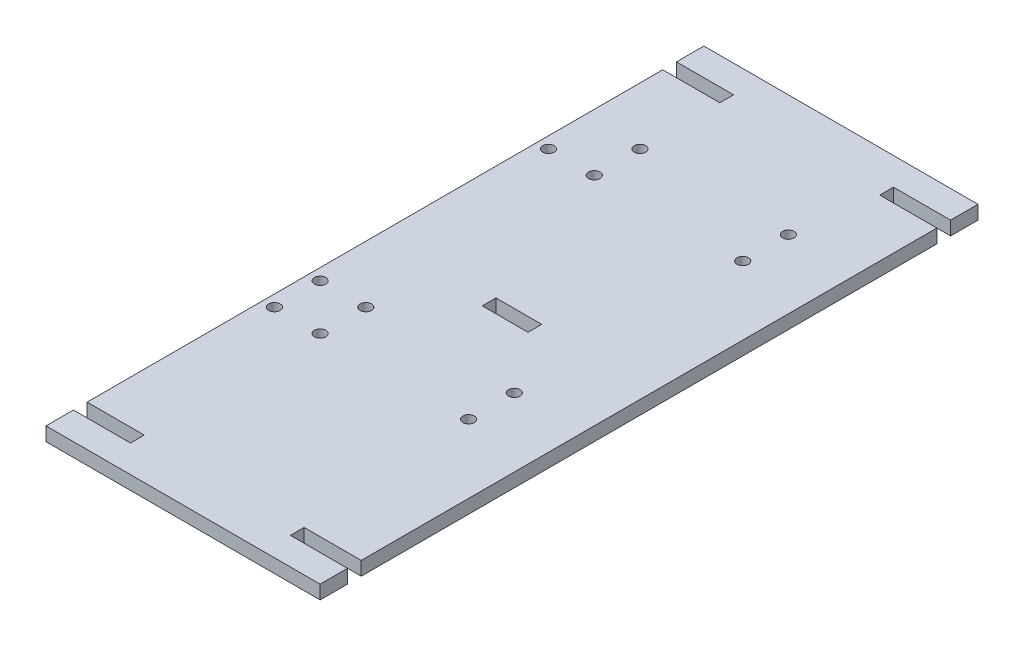
SolidWorks part; units mm, degrees
ref_plane "Front" through (0, 0, 0) normal (0, 0, 1) x (1, 0, 0)
ref_plane "Top" through (0, 0, 0) normal (0, 1, 0) x (1, 0, 0)
ref_plane "Right" through (0, 0, 0) normal (1, 0, 0) x (0, 0, -1)
sketch "Sketch1" plane through (0, 0, 0) normal (0, 1, 0) x (1, 0, 0)
  line L1 (0, 0) -> (-120, 0)
  line L2 (0, 0) -> (0, 288)
  line L3 (0, 288) -> (-120, 288)
  line L4 (-120, 0) -> (-120, 288)
  dimension "D1" = 288
  dimension "D2" = 120
extrude "Boss-Extrude1" add sketch "Sketch1" along normal blind 6
sketch "Sketch2" plane through (0, 6, 0) normal (0, 1, 0) x (1, 0, 0)
  line L0 (-120, 288) -> (-120, 0) construction
  line L1 (-120, 276) -> (-95, 276)
  line L2 (-120, 276) -> (-120, 270)
  line L3 (-120, 270) -> (-95, 270)
  line L4 (-95, 276) -> (-95, 270)
  line L5 (0, 288) -> (-120, 288) construction
  dimension "D1" = 6
  dimension "D2" = 25
  dimension "D3" = 12
extrude "Cut-Extrude1" cut sketch "Sketch2" against normal through all
pattern_linear "LPattern1" count 2 spacing 258 along (0, 0, 1) count 2 spacing 95 along (1, 0, 0) of "Cut-Extrude1"
sketch "Sketch3" plane through (0, 6, 0) normal (0, 1, 0) x (1, 0, 0)
  line L0 (-60, 288) -> (-60, 0) construction
  line L1 (0, 288) -> (-120, 288) construction
  line L2 (-120, 0) -> (0, 0) construction
  line L3 (-120, 144) -> (0, 144) construction
  line L4 (-120, 270) -> (-120, 18) construction
  line L5 (0, 18) -> (0, 270) construction
  line L7 (-70, 141) -> (-50, 141)
  line L8 (-70, 141) -> (-70, 147)
  line L9 (-70, 147) -> (-50, 147)
  line L10 (-50, 141) -> (-50, 147)
  line L11 (-70, 141) -> (-50, 147) construction
  line L12 (-70, 147) -> (-50, 141) construction
  point P12 (-60, 144)
  dimension "D1" = 6
  dimension "D2" = 20
extrude "Cut-Extrude2" cut sketch "Sketch3" against normal blind 10
sketch "Sketch4" plane through (0, 6, 0) normal (0, 1, 0) x (1, 0, 0)
  line L0 (-105, 115) -> (-105, 215) construction
  line L1 (-30, 235) -> (-30, 215) construction
  line L2 (-95, 225) -> (-30, 225) construction
  line L3 (-95, 105) -> (-30, 105) construction
  line L4 (-70, 141) -> (-50, 141) construction
  line L5 (-105, 105) -> (-105, 55) construction
  line L6 (-120, 270) -> (-120, 18) construction
  line L7 (-115, 115) -> (-95, 115) construction
  line L8 (-95, 115) -> (-95, 95) construction
  line L9 (-30, 115) -> (-30, 95) construction
  line L10 (-115, 115) -> (-115, 95) construction
  line L11 (-115, 95) -> (-95, 95) construction
  arc A0 (-105, 115) -> (-95, 105) centre (-95, 115) ccw construction
  arc A1 (-105, 215) -> (-95, 225) centre (-95, 215) cw construction
  circle A2 centre (-30, 235) radius 2.5
  circle A3 centre (-30, 215) radius 2.5
  circle A4 centre (-95, 235) radius 2.5
  circle A5 centre (-95, 215) radius 2.5
  circle A6 centre (-115, 215) radius 2.5
  circle A13 centre (-95, 115) radius 2.5
  circle A14 centre (-115, 115) radius 2.5
  circle A15 centre (-95, 95) radius 2.5
  circle A16 centre (-30, 115) radius 2.5
  circle A17 centre (-30, 95) radius 2.5
  circle A18 centre (-115, 95) radius 2.5
  point P11 (-120, 144)
  point P15 (-105, 225)
  point P17 (-95, 225)
  point P18 (-105, 215)
  point P19 (-105, 115)
  point P20 (-95, 105)
  point P21 (-30, 105)
  point P23 (-30, 225)
  point P26 (-95, 105)
  point P32 (-105, 115)
  point P35 (-95, 215)
  point P39 (-30, 105)
  dimension "D6" = 10
  dimension "D7" = 5
  dimension "D1" = 36
  dimension "D2" = 50
  dimension "D3" = 75
  dimension "D4" = 15
  dimension "D5" = 120
  dimension "D8" = 20
  dimension "D9" = 2
  dimension "D10" = 2
extrude "Cut-Extrude4" cut sketch "Sketch4" against normal blind 10
